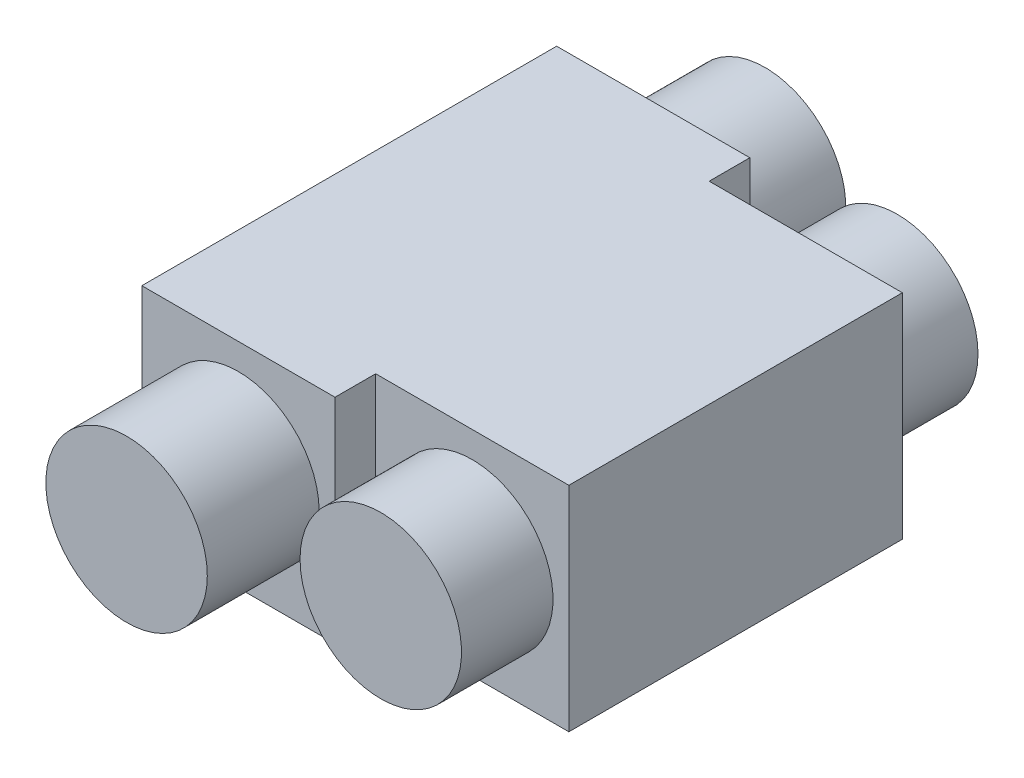
SolidWorks part; units mm, degrees
other "标注1"
sketch "草图6" plane through (-95, 0, 157) normal (0, 0, 1) x (1, 0, 0)
ref_plane "前视基准面" through (0, 0, 0) normal (0, 0, 1) x (1, 0, 0)
ref_plane "上视基准面" through (0, 0, 0) normal (0, 1, 0) x (1, 0, 0)
ref_plane "右视基准面" through (0, 0, 0) normal (1, 0, 0) x (0, 0, -1)
other "质心 (COM)"
sketch "草图1" plane through (0, 0, 0) normal (0, 1, 0) x (1, 0, 0)
  line L0 (-95, -102) -> (0, -102)
  line L1 (-95, -82) -> (95, -82)
  line L2 (-95, -82) -> (-95, 82)
  line L3 (-95, 82) -> (95, 82)
  line L4 (95, -82) -> (95, 82)
  line L5 (-95, -82) -> (95, 82) construction
  line L6 (-95, 82) -> (95, -82) construction
  line L7 (-95, -102) -> (-95, 102)
  line L8 (0, -102) -> (0, 102)
  line L9 (-95, 102) -> (0, 102)
  point P0 (0, 0)
  point P6 (-95, 0)
  dimension "D1" = 190
  dimension "D2" = 164
  dimension "D3" = 204
  dimension "D4" = 102
  dimension "D5" = 95
extrude "凸台-拉伸2" add sketch "草图1" along normal blind 105 contours L4 L3 L2 L1
extrude "凸台-拉伸3" add sketch "草图1<5>" along normal blind 105 contours L0 L8 L9 L7
sketch "草图1<5>" plane through (0, 0, 0) normal (0, 1, 0) x (1, 0, 0) same geometry as "草图1"
sketch "草图2" plane through (0, 0, 102) normal (0, 0, 1) x (1, 0, 0)
  line L0 (-95, 105) -> (-95, 0) construction
  line L1 (-95, 0) -> (0, 0) construction
  circle A0 centre (-47.5, 52.5) radius 39.7
  point P4 (0, 0)
  dimension "D2" = 79.4
  dimension "D1" = 47.5
  dimension "D3" = 52.5
extrude "凸台-拉伸4" add sketch "草图2" along normal blind 55
sketch "草图3" plane through (0, 0, 82) normal (0, 0, 1) x (1, 0, 0)
  line L0 (95, 105) -> (95, 0) construction
  line L1 (0, 0) -> (95, 0) construction
  circle A0 centre (47.5, 52.5) radius 39.7
  dimension "D2" = 79.4
  dimension "D1" = 47.5
  dimension "D3" = 52.5
extrude "凸台-拉伸5" add sketch "草图3" along normal blind 45
sketch "草图4" plane through (0, 0, -102) normal (0, 0, -1) x (-1, 0, 0)
  line L0 (95, 105) -> (95, 0) construction
  line L1 (95, 0) -> (0, 0) construction
  circle A0 centre (47.5, 52.5) radius 39.7
  dimension "D2" = 79.4
  dimension "D1" = 47.5
  dimension "D3" = 52.5
extrude "凸台-拉伸6" add sketch "草图4" along normal blind 55
sketch "草图5" plane through (0, 0, -82) normal (0, 0, -1) x (-1, 0, 0)
  line L0 (-95, 105) -> (-95, 0) construction
  line L1 (0, 0) -> (-95, 0) construction
  circle A0 centre (-47.5, 52.5) radius 39.7
  dimension "D2" = 79.4
  dimension "D1" = 47.5
  dimension "D3" = 52.5
extrude "凸台-拉伸7" add sketch "草图5" along normal blind 45
